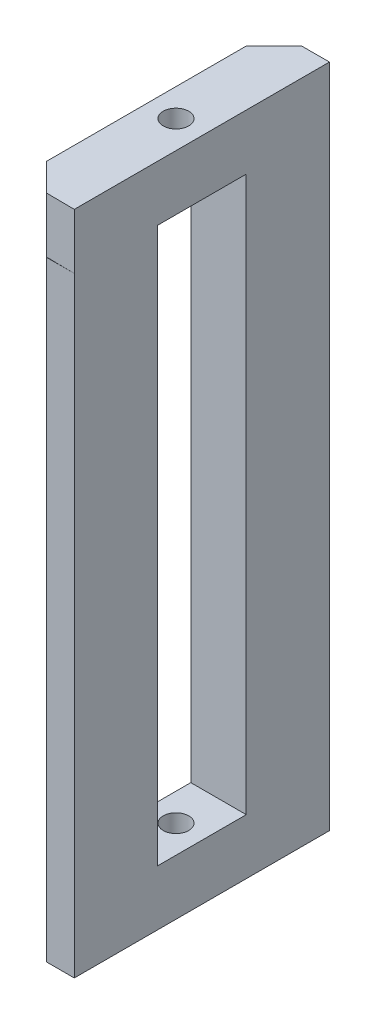
SolidWorks part; units mm, degrees
ref_plane "Спереди" through (0, 0, 0) normal (0, 0, 1) x (1, 0, 0)
ref_plane "Сверху" through (0, 0, 0) normal (0, 1, 0) x (1, 0, 0)
ref_plane "Справа" through (0, 0, 0) normal (1, 0, 0) x (0, 0, -1)
ref_plane "Плоскость4" through (0, 116.196, 0) normal (0, 1, 0) x (1, 0, 0)
sketch "Эскиз1" plane through (0, 116.196, 0) normal (0, 1, 0) x (1, 0, 0)
  line L3 (-8.441, -97.5231) -> (-8.441, -81.5231)
  line L4 (-8.441, -81.5231) -> (-8.441, -66.5231)
  line L6 (-8.441, -97.5231) -> (-8.441, -112.5231)
  line L8 (-8.441, -112.5231) -> (1.559, -112.5231)
  line L9 (1.559, -110.7731) -> (1.559, -130.7731) construction
  line L10 (1.559, -112.5231) -> (1.559, -66.5231)
  line L11 (1.559, -48.2731) -> (1.559, -68.2731) construction
  line L12 (1.559, -66.5231) -> (-8.441, -66.5231)
  circle A0 centre (-3.441, -89.1878) radius 2.3
extrude "Бобышка-Вытянуть1" add sketch "Эскиз1" along normal blind 10
ref_plane "Плоскость5" through (0, 126.196, 0) normal (0, 1, 0) x (1, 0, 0)
sketch "Эскиз2" plane through (0, 126.196, 0) normal (0, 1, 0) x (1, 0, 0)
  line L0 (-8.441, -81.5231) -> (1.559, -81.5231)
  line L2 (1.559, -81.5231) -> (1.559, -66.5231)
  line L3 (1.559, -68.2731) -> (1.559, -75.5231) construction
  line L4 (1.559, -66.5231) -> (-8.441, -66.5231)
  line L5 (-8.441, -66.5231) -> (-8.441, -81.5231)
  line L6 (-8.441, -97.5231) -> (1.559, -97.5231)
  line L8 (1.559, -97.5231) -> (1.559, -112.5231)
  line L9 (1.559, -103.5231) -> (1.559, -110.7731) construction
  line L10 (1.559, -112.5231) -> (-8.441, -112.5231)
  line L11 (-8.441, -112.5231) -> (-8.441, -97.5231)
  point P0 (0, 0)
extrude "Бобышка-Вытянуть2" add sketch "Эскиз2" along normal blind 100
ref_plane "Плоскость6" through (0, 226.196, 0) normal (0, 1, 0) x (1, 0, 0)
sketch "Эскиз3" plane through (0, 226.196, 0) normal (0, 1, 0) x (1, 0, 0)
  line L0 (-8.441, -66.5439) -> (-8.441, -112.4255)
  line L1 (-8.441, -66.5231) -> (-8.441, -81.5231) construction
  line L2 (-8.441, -112.4255) -> (1.559, -112.5231)
  line L3 (1.559, -112.5231) -> (1.559, -66.5231)
  line L4 (1.559, -66.5231) -> (-8.441, -66.5439)
  circle A0 centre (-3.441, -89.1878) radius 2.3
  point P8 (0, 0)
  point P13 (0, 0)
extrude "Бобышка-Вытянуть3" add sketch "Эскиз3" along normal blind 10
chamfer "Фаска1" distance 5 angle 45 2 edges at (-8.441, 171.196, 66.5231) (-8.441, 171.196, 112.5231)
